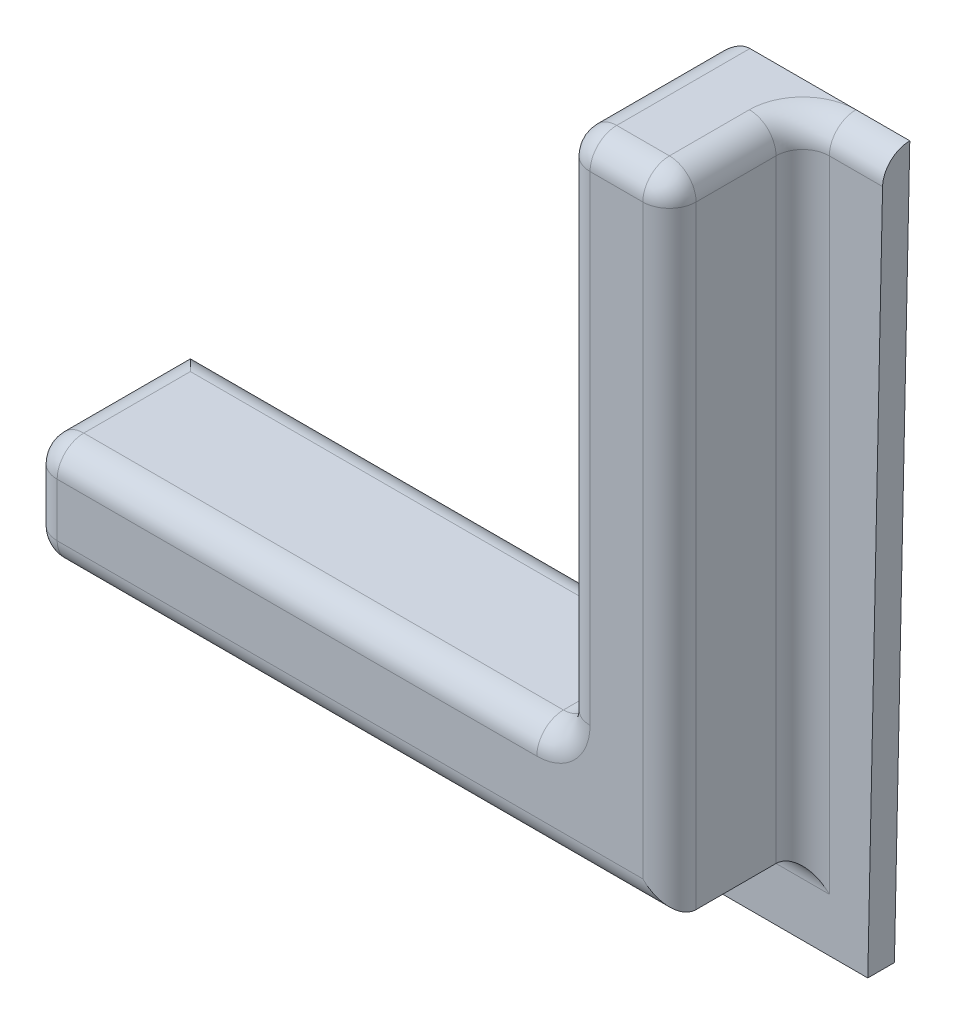
SolidWorks part; units mm, degrees
material "1060 合金"
ref_plane "前视基准面" through (0, 0, 0) normal (0, 0, 1) x (1, 0, 0)
ref_plane "上视基准面" through (0, 0, 0) normal (0, 1, 0) x (1, 0, 0)
ref_plane "右视基准面" through (0, 0, 0) normal (1, 0, 0) x (0, 0, -1)
sketch "草图1" plane through (0, 0, 0) normal (0, 0, 1) x (1, 0, 0)
  line L0 (-22.6268, 6.9987) -> (-21.6268, 6.9987)
  line L1 (-21.6268, 6.9987) -> (-21.6268, 7.9987)
  line L2 (-21.6268, 7.9987) -> (-21.4268, 7.9987)
  line L3 (-21.4268, 7.9987) -> (-21.4268, 6.7987)
  line L4 (-21.4268, 6.7987) -> (-22.6268, 6.7987)
  line L5 (-22.6268, 6.7987) -> (-22.6268, 6.9987)
  line L6 (-22.6268, 6.7987) -> (-22.6268, 6.6487)
  line L7 (-22.6268, 6.6487) -> (-21.3057, 6.6487)
  line L8 (-21.4268, 7.9987) -> (-21.2768, 7.9987)
  line L9 (-21.2768, 7.9987) -> (-21.3057, 6.6487)
extrude "凸台-拉伸1" add sketch "草图1" along normal blind 0.3 contours L5 L4 L3 L2 L1 L0 | L9 L8 L3 L4 L6 L7 region at (-22.1268, 6.9817, 0) region at (-22.0268, 6.7796, 0)
sketch "草图2" plane through (0, 0, 0.3) normal (0, 0, 1) x (1, 0, 0)
  line L0 (-21.2768, 7.9987) -> (-21.3057, 6.6487)
  line L1 (-21.2768, 7.9987) -> (-21.3057, 6.6487) construction
  line L2 (-21.3057, 6.6487) -> (-22.6268, 6.6487)
  line L3 (-22.6268, 6.6487) -> (-22.6268, 6.7987)
  line L4 (-22.6268, 6.6487) -> (-22.6268, 6.9987) construction
  line L5 (-22.6268, 6.7987) -> (-21.4779, 6.7987)
  line L6 (-21.4779, 6.7987) -> (-21.4279, 6.7987)
  line L7 (-21.4279, 6.7987) -> (-21.4279, 7.9987)
  line L8 (-21.6268, 7.9987) -> (-21.2768, 7.9987) construction
  line L9 (-21.4279, 7.9987) -> (-21.2768, 7.9987)
  line L10 (-21.2768, 7.9987) -> (-21.2707, 7.9951)
  line M2 (-22.6268, 6.9987) -> (-22.6268, 6.6487)
  line M3 (-22.6268, 6.6487) -> (-21.3057, 6.6487)
  line M4 (-21.3057, 6.6487) -> (-21.2768, 7.9987)
  line M5 (-21.2768, 7.9987) -> (-21.6268, 7.9987)
extrude "切除-拉伸1" cut sketch "草图2" against normal blind 0.25 contours L7 L6 L5 M2 M3 M4 M5 region at (-21.3103, 7.3241, 0.3)
fillet "圆角1" radius 0.05 17 edges at (-22.6268, 6.7237, 0.05) (-21.3523, 7.9987, 0.05) (-22.6268, 6.8987, 0.3) (-22.1268, 6.9987, 0.3) (-21.5273, 7.9987, 0.3) (-21.4279, 7.3987, 0.3) (-22.0273, 6.7987, 0.3) (-21.6268, 7.9987, 0.15) (-21.6268, 7.4987, 0.3) (-21.6268, 6.9987, 0.15) (-21.6268, 7.4987, 0) (-22.6268, 6.7987, 0.175) (-22.6268, 6.9987, 0.15) (-21.4279, 7.9987, 0.175) (-22.0273, 6.7987, 0.05) (-22.1268, 6.9987, 0) (-21.4279, 7.3987, 0.05)
